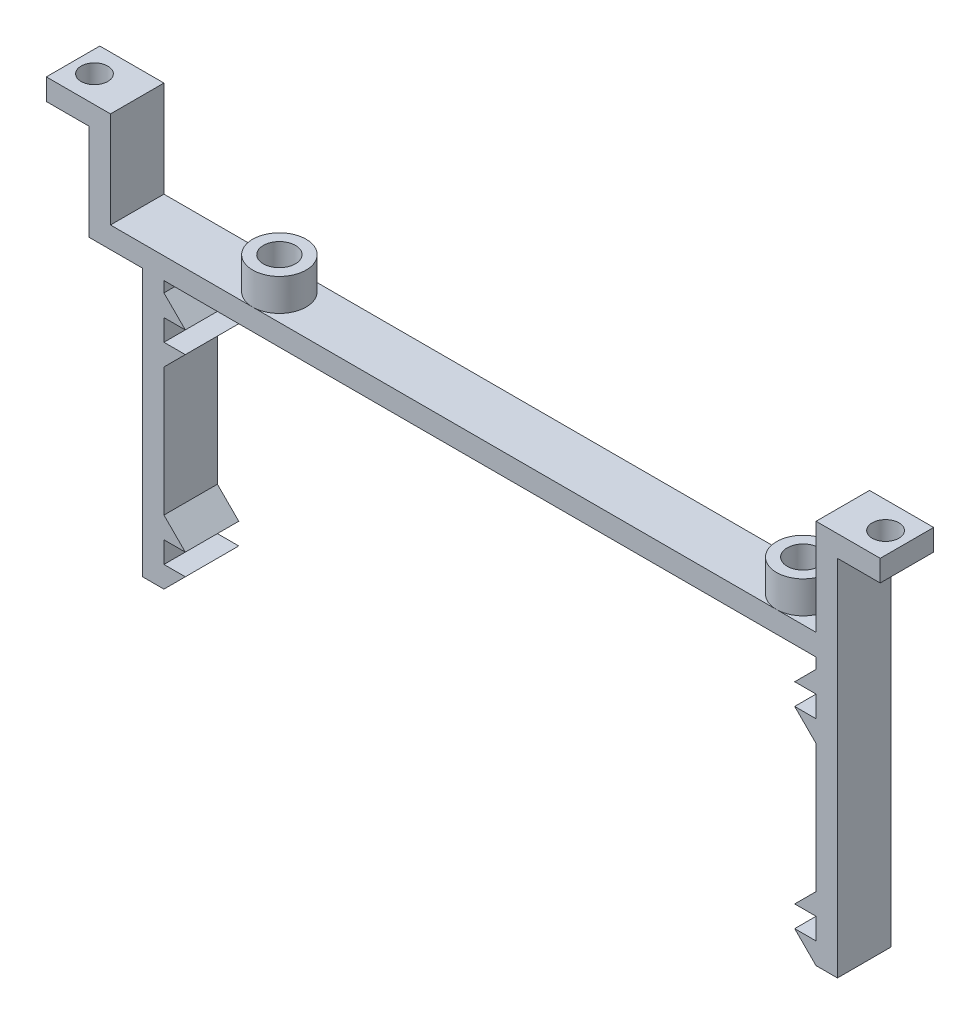
SolidWorks part; units mm, degrees
ref_plane "Front Plane" through (0, 0, 0) normal (0, 0, 1) x (1, 0, 0)
ref_plane "Top Plane" through (0, 0, 0) normal (0, 1, 0) x (1, 0, 0)
ref_plane "Right Plane" through (0, 0, 0) normal (1, 0, 0) x (0, 0, -1)
sketch "Sketch1" plane through (0, 0, 0) normal (0, 1, 0) x (1, 0, 0)
  line L1 (-33, 2.5) -> (33, 2.5)
  line L2 (-33, 2.5) -> (-33, -2.5)
  line L3 (-33, -2.5) -> (33, -2.5)
  line L4 (33, 2.5) -> (33, -2.5)
  line L5 (-33, 2.5) -> (33, -2.5) construction
  line L6 (-33, -2.5) -> (33, 2.5) construction
  point P0 (0, 0)
  dimension "D1" = 5
  dimension "D2" = 66
base flange "Base-Flange1" sketch "Sketch1" thickness 2 reverse thickness direction no parameters "D1"=4
sketch "Sketch2" plane through (0, 0, 0) normal (0, -1, 0) x (-1, 0, 0)
  line L0 (-29.3, -1.375) -> (-29.3, 1.375) construction
  line L1 (19.7, -1.375) -> (19.7, 1.375) construction
  circle A0 centre (-29.3, 0) radius 1.375 construction
  circle A1 centre (19.7, 0) radius 1.375 construction
  circle A2 centre (19.7, 0) radius 2.5
  circle A3 centre (-29.3, 0) radius 2.5
  dimension "D1" = 5
  dimension "D2" = 5
extrude "Boss-Extrude1" add sketch "Sketch2" against normal blind 3
sketch "Sketch3" plane through (0, -2, 0) normal (0, -1, 0) x (-1, 0, 0)
  line L1 (-33, -2.5) -> (-35, -2.5)
  line L2 (-33, -2.5) -> (-33, 2.5)
  line L3 (-33, 2.5) -> (-35, 2.5)
  line L4 (-35, -2.5) -> (-35, 2.5)
  line L5 (-34, 2.5) -> (-34, -2.5) construction
  line L6 (-33, 0) -> (-35, 0) construction
  point P184 (-34, 0)
  dimension "D1" = 2
extrude "Boss-Extrude2" add sketch "Sketch3" against normal blind 11
sketch "Sketch4" plane through (0, 9, 0) normal (0, 1, 0) x (1, 0, 0)
  line L1 (33, 2.5) -> (39, 2.5)
  line L2 (33, 2.5) -> (33, -2.5)
  line L3 (33, -2.5) -> (39, -2.5)
  line L4 (39, 2.5) -> (39, -2.5)
  line L5 (36, -2.5) -> (36, 2.5) construction
  line L6 (33, 0) -> (39, 0) construction
  point P120 (36, 0)
  dimension "D1" = 6
extrude "Boss-Extrude3" add sketch "Sketch4" against normal blind 2
mirror "Mirror1" about plane through (0, 0, 0) normal (1, 0, 0) of "Boss-Extrude3", "Boss-Extrude2"
sketch "Sketch5" plane through (0, 3, 0) normal (0, 1, 0) x (1, 0, 0)
  circle A0 centre (-19.7, 0) radius 1.5
  circle A1 centre (29.3, 0) radius 1.5
  dimension "D1" = 3
  dimension "D2" = 3
extrude "Cut-Extrude1" cut sketch "Sketch5" against normal through all normal cut yes
sketch "Sketch6" plane through (0, 9, 0) normal (0, 1, 0) x (1, 0, 0)
  line L0 (-39, 0) -> (-37, 0) construction
  line L1 (-39, -2.5) -> (-39, 2.5) construction
  line L2 (0, 0) -> (0, 18.8568) construction
  circle A0 centre (-37, 0) radius 1.25
  circle A1 centre (37, 0) radius 1.25
  dimension "D1" = 2.5
  dimension "D2" = 2
extrude "Cut-Extrude2" cut sketch "Sketch6" against normal through all normal cut yes
sketch "Sketch7" plane through (0, -2, 0) normal (0, -1, 0) x (-1, 0, 0)
  line L0 (35, -2.5) -> (-35, -2.5) construction
  line L1 (30, 2.5) -> (28, 2.5)
  line L2 (30, 2.5) -> (30, -2.5)
  line L3 (30, -2.5) -> (28, -2.5)
  line L4 (28, 2.5) -> (28, -2.5)
  line L5 (29, -2.5) -> (29, 2.5) construction
  line L6 (30, 0) -> (28, 0) construction
  line L7 (35, 2.5) -> (35, -2.5) construction
  point P104 (29, 0)
  dimension "D1" = 2
  dimension "D2" = 5
extrude "Boss-Extrude4" add sketch "Sketch7" along normal blind 25
sketch "Sketch8" plane through (0, 0, 2.5) normal (0, 0, 1) x (1, 0, 0)
  line L0 (-28, -3) -> (-26, -5)
  line L1 (-28, -27) -> (-28, -2) construction
  line L2 (-26, -5) -> (-28, -5)
  line L3 (-28, -5) -> (-28, -3)
  line L4 (-28, -2) -> (35, -2) construction
  line L5 (-28, -5) -> (-28, -7) construction
  line L6 (-28, -7) -> (-26, -7)
  line L7 (-26, -7) -> (-28, -9)
  line L8 (-28, -9) -> (-28, -7)
  line L9 (-28, -6) -> (-28, -24) construction
  line L10 (-28, -24) -> (-30.0471, -24) construction
  line L11 (-28, -15) -> (-20.8093, -15) construction
  line L12 (-28, -21) -> (-28, -23)
  line L13 (-26, -23) -> (-28, -21)
  line L14 (-28, -23) -> (-26, -23)
  line L15 (-28, -25) -> (-28, -27)
  line L16 (-28, -27) -> (-26, -25)
  line L17 (-26, -25) -> (-28, -25)
  point P15 (-28, -4)
  point P22 (-28, -26)
  dimension "D1" = 2
  dimension "D2" = 2
  dimension "D3" = 1
  dimension "D4" = 2
  dimension "D5" = 2
  dimension "D6" = 2
  dimension "D7" = 18
extrude "Boss-Extrude5" add sketch "Sketch8" against normal up to surface (5 mm away)
ref_plane "Plane1" through (2.5, 0, 0) normal (1, 0, 0) x (0, 0, -1)
mirror "Mirror2" about plane through (2.5, 0, 0) normal (1, 0, 0) of "Boss-Extrude5", "Boss-Extrude4"
sketch "Bend-Lines1" [suppressed] plane through (0, 0, 0) normal (0, 1, 0) x (1, 0, 0)
sketch "Bounding-Box1" [suppressed] plane through (0, 0, 0) normal (0, 1, 0) x (1, 0, 0)
sheet metal parameters "Sheet-Metal1" thickness 2 parameters "D1"=4
flat pattern "Flat-Pattern1" [suppressed]
sketch "Bend-Lines2" plane through (0, 0, 0) normal (0, 1, 0) x (1, 0, 0)
sketch3d "Bounding-Box2" [suppressed]
  line L0 (39, -2.5, 0) -> (-39, -2.5, 0) construction
  line L1 (39, 2.5, 0) -> (-39, 2.5, 0) construction
  line L2 (39, -2.5, 0) -> (39, 2.5, 0) construction
  line L3 (-39, -2.5, 0) -> (-39, 2.5, 0) construction
sheet metal parameters "Sheet-Metal5" thickness 2 parameters "D1"=4
flat pattern "Flat-Pattern1"
sketch "Bend-Lines2" plane through (0, 0, 0) normal (0, 1, 0) x (1, 0, 0)
sketch3d "Bounding-Box2" [suppressed]
  line L0 (34, -2.5, 0) -> (-34, -2.5, 0) construction
  line L1 (34, 2.5, 0) -> (-34, 2.5, 0) construction
  line L2 (34, -2.5, 0) -> (34, 2.5, 0) construction
  line L3 (-34, -2.5, 0) -> (-34, 2.5, 0) construction
sheet metal parameters "Sheet-Metal6" thickness 2 parameters "D1"=4
flat pattern "Flat-Pattern1"
sketch "Bend-Lines2" plane through (0, 0, 0) normal (0, 1, 0) x (1, 0, 0)
sketch3d "Bounding-Box2" [suppressed]
  line L0 (34, -2.5, 0) -> (-34, -2.5, 0) construction
  line L1 (34, 2.5, 0) -> (-34, 2.5, 0) construction
  line L2 (34, -2.5, 0) -> (34, 2.5, 0) construction
  line L3 (-34, -2.5, 0) -> (-34, 2.5, 0) construction
sheet metal parameters "Sheet-Metal7" thickness 2 parameters "D1"=4
flat pattern "Flat-Pattern1"
sketch "Bend-Lines2" plane through (0, 0, 0) normal (0, 1, 0) x (1, 0, 0)
sketch3d "Bounding-Box2" [suppressed]
  line L0 (33, -2.5, 0) -> (-33, -2.5, 0) construction
  line L1 (33, 2.5, 0) -> (-33, 2.5, 0) construction
  line L2 (33, -2.5, 0) -> (33, 2.5, 0) construction
  line L3 (-33, -2.5, 0) -> (-33, 2.5, 0) construction
sheet metal parameters "Sheet-Metal8" thickness 2 parameters "D1"=4
flat pattern "Flat-Pattern1"
sketch "Bend-Lines2" plane through (0, 0, 0) normal (0, 1, 0) x (1, 0, 0)
sketch3d "Bounding-Box2" [suppressed]
  line L0 (33, -2.5, 0) -> (-33, -2.5, 0) construction
  line L1 (33, 2.5, 0) -> (-33, 2.5, 0) construction
  line L2 (33, -2.5, 0) -> (33, 2.5, 0) construction
  line L3 (-33, -2.5, 0) -> (-33, 2.5, 0) construction
sheet metal parameters "Sheet-Metal9" thickness 2 parameters "D1"=4
flat pattern "Flat-Pattern1"
sketch "Bend-Lines2" plane through (0, 0, 0) normal (0, 1, 0) x (1, 0, 0)
sketch3d "Bounding-Box2" [suppressed]
  line L0 (33, -2.5, 0) -> (-33, -2.5, 0) construction
  line L1 (33, 2.5, 0) -> (-33, 2.5, 0) construction
  line L2 (33, -2.5, 0) -> (33, 2.5, 0) construction
  line L3 (-33, -2.5, 0) -> (-33, 2.5, 0) construction
sheet metal parameters "Sheet-Metal10" thickness 2 parameters "D1"=4
flat pattern "Flat-Pattern1"
sketch "Bend-Lines2" plane through (0, 0, 0) normal (0, 1, 0) x (1, 0, 0)
sketch3d "Bounding-Box2" [suppressed]
  line L0 (33, -2.5, 0) -> (-33, -2.5, 0) construction
  line L1 (33, 2.5, 0) -> (-33, 2.5, 0) construction
  line L2 (33, -2.5, 0) -> (33, 2.5, 0) construction
  line L3 (-33, -2.5, 0) -> (-33, 2.5, 0) construction
sheet metal parameters "Sheet-Metal11" thickness 2 parameters "D1"=4
flat pattern "Flat-Pattern1"
sketch "Bend-Lines2" plane through (0, 0, 0) normal (0, 1, 0) x (1, 0, 0)
sketch3d "Bounding-Box2" [suppressed]
  line L0 (33, -2.5, 0) -> (-33, -2.5, 0) construction
  line L1 (33, 2.5, 0) -> (-33, 2.5, 0) construction
  line L2 (33, -2.5, 0) -> (33, 2.5, 0) construction
  line L3 (-33, -2.5, 0) -> (-33, 2.5, 0) construction
sheet metal parameters "Sheet-Metal12" thickness 2 parameters "D1"=4
flat pattern "Flat-Pattern1"
sketch "Bend-Lines2" plane through (0, 0, 0) normal (0, 1, 0) x (1, 0, 0)
sketch3d "Bounding-Box2" [suppressed]
  line L0 (33, -2.5, 0) -> (-33, -2.5, 0) construction
  line L1 (33, 2.5, 0) -> (-33, 2.5, 0) construction
  line L2 (33, -2.5, 0) -> (33, 2.5, 0) construction
  line L3 (-33, -2.5, 0) -> (-33, 2.5, 0) construction
sheet metal parameters "Sheet-Metal14" thickness 2 parameters "D1"=4
flat pattern "Flat-Pattern1"
sketch "Bend-Lines2" plane through (0, 0, 0) normal (0, 1, 0) x (1, 0, 0)
sketch3d "Bounding-Box2" [suppressed]
  line L0 (33, -2.5, 0) -> (-33, -2.5, 0) construction
  line L1 (33, 2.5, 0) -> (-33, 2.5, 0) construction
  line L2 (33, -2.5, 0) -> (33, 2.5, 0) construction
  line L3 (-33, -2.5, 0) -> (-33, 2.5, 0) construction
